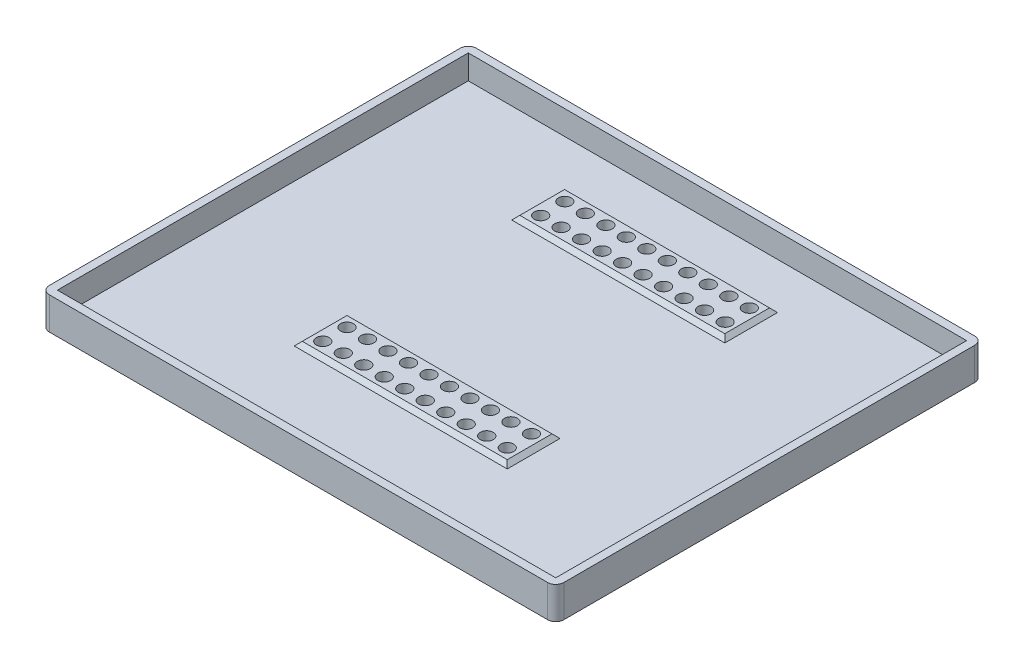
SolidWorks part; units mm, degrees
ref_plane "前视基准面" through (0, 0, 0) normal (0, 0, 1) x (1, 0, 0)
ref_plane "上视基准面" through (0, 0, 0) normal (0, 1, 0) x (1, 0, 0)
ref_plane "右视基准面" through (0, 0, 0) normal (1, 0, 0) x (0, 0, -1)
other "Configuration Table"
sketch "草图1" plane through (0, 0, 0) normal (0, 1, 0) x (1, 0, 0)
  line L1 (-39.7539, 20.0048) -> (24.0061, 20.0048)
  line L2 (-39.7539, 20.0048) -> (-39.7539, -32.9152)
  line L3 (-39.7539, -32.9152) -> (24.0061, -32.9152)
  line L4 (24.0061, 20.0048) -> (24.0061, -32.9152)
  dimension "D1" = 52.92
  dimension "D2" = 63.76
extrude "凸台-拉伸1" add sketch "草图1" along normal blind 1
fillet "圆角1" radius 1 4 edges at (24.0061, 0.5, 32.9152) (24.0061, 0.5, -20.0048) (-39.7539, 0.5, -20.0048) (-39.7539, 0.5, 32.9152)
sketch "草图2" plane through (0, 1, 0) normal (0, 1, 0) x (1, 0, 0)
  line L0 (23.0061, 20.0048) -> (-38.7539, 20.0048) construction
  line L1 (-20.6244, 12.8048) -> (4.7756, 12.8048)
  line L2 (-20.6244, 12.8048) -> (-20.6244, 7.2648)
  line L3 (-20.6244, 7.2648) -> (4.7756, 7.2648)
  line L4 (4.7756, 12.8048) -> (4.7756, 7.2648)
  line L5 (-20.5839, -14.1952) -> (4.8161, -14.1952)
  line L6 (-20.5839, -14.1952) -> (-20.5839, -19.7352)
  line L7 (-20.5839, -19.7352) -> (4.8161, -19.7352)
  line L8 (4.8161, -14.1952) -> (4.8161, -19.7352)
  line L9 (24.0061, -31.9152) -> (24.0061, 19.0048) construction
  line L10 (-38.7539, -32.9152) -> (23.0061, -32.9152) construction
  dimension "D1" = 25.4
  dimension "D2" = 5.54
  dimension "D3" = 7.2
  dimension "D4" = 19.2305
  dimension "D5" = 19.19
  dimension "D6" = 13.18
extrude "凸台-拉伸2" add sketch "草图2" along normal blind 0.5
chamfer "倒角1" distance 0.5 angle 45 8 edges at (4.8161, 1, 16.9652) (-7.8839, 1, 14.1952) (-7.8839, 1, 19.7352) (-20.5839, 1, 16.9652) (-20.6244, 1, -10.0348) (-7.9244, 1, -12.8048) (4.7756, 1, -10.0348) (-7.9244, 1, -7.2648)
sketch "草图3" plane through (0, 0, 0) normal (0, -1, 0) x (1, 0, 0)
  line L0 (-39.7539, -19.0048) -> (-39.7539, 31.9152) construction
  line L1 (-38.7539, 32.9152) -> (23.0061, 32.9152) construction
  line L2 (23.0061, -20.0048) -> (-38.7539, -20.0048) construction
  line L3 (-19.3139, -8.5348) -> (-16.7739, -8.5348) construction
  line L4 (-19.3139, -8.5348) -> (-19.3139, -11.5348) construction
  circle A0 centre (-19.3139, 18.4652) radius 0.8
  circle A1 centre (-16.7739, 18.4652) radius 0.8
  circle A2 centre (-14.2339, 18.4652) radius 0.8
  circle A3 centre (-11.6939, 18.4652) radius 0.8
  circle A4 centre (-9.1539, 18.4652) radius 0.8
  circle A5 centre (-6.6139, 18.4652) radius 0.8
  circle A6 centre (-4.0739, 18.4652) radius 0.8
  circle A7 centre (-1.5339, 18.4652) radius 0.8
  circle A8 centre (1.0061, 18.4652) radius 0.8
  circle A9 centre (3.5461, 18.4652) radius 0.8
  circle A10 centre (-16.7739, 15.4652) radius 0.8
  circle A11 centre (-14.2339, 15.4652) radius 0.8
  circle A12 centre (-11.6939, 15.4652) radius 0.8
  circle A13 centre (-9.1539, 15.4652) radius 0.8
  circle A14 centre (-6.6139, 15.4652) radius 0.8
  circle A15 centre (-4.0739, 15.4652) radius 0.8
  circle A16 centre (-1.5339, 15.4652) radius 0.8
  circle A17 centre (1.0061, 15.4652) radius 0.8
  circle A18 centre (3.5461, 15.4652) radius 0.8
  circle A19 centre (-19.3139, 15.4652) radius 0.8
  circle A20 centre (-19.3139, -8.5348) radius 0.8
  circle A21 centre (-16.7739, -8.5348) radius 0.8
  circle A22 centre (-14.2339, -8.5348) radius 0.8
  circle A23 centre (-11.6939, -8.5348) radius 0.8
  circle A24 centre (-9.1539, -8.5348) radius 0.8
  circle A25 centre (-6.6139, -8.5348) radius 0.8
  circle A26 centre (-4.0739, -8.5348) radius 0.8
  circle A27 centre (-1.5339, -8.5348) radius 0.8
  circle A28 centre (1.0061, -8.5348) radius 0.8
  circle A29 centre (3.5461, -8.5348) radius 0.8
  circle A30 centre (-16.7739, -11.5348) radius 0.8
  circle A31 centre (-14.2339, -11.5348) radius 0.8
  circle A32 centre (-11.6939, -11.5348) radius 0.8
  circle A33 centre (-9.1539, -11.5348) radius 0.8
  circle A34 centre (-6.6139, -11.5348) radius 0.8
  circle A35 centre (-4.0739, -11.5348) radius 0.8
  circle A36 centre (-1.5339, -11.5348) radius 0.8
  circle A37 centre (1.0061, -11.5348) radius 0.8
  circle A38 centre (3.5461, -11.5348) radius 0.8
  circle A39 centre (-19.3139, -11.5348) radius 0.8
  dimension "D1" = 1.6
  dimension "D6" = 11.47
  dimension "D2" = 20.44
  dimension "D3" = 14.45
  dimension "D4" = 10
  dimension "D5" = 2
  dimension "D9" = 2.54
  dimension "D10" = 3
  dimension "D7" = 10
  dimension "D8" = 2
extrude "切除-拉伸2" cut sketch "草图3" against normal through all
sketch "草图4" plane through (0, 1, 0) normal (0, 1, 0) x (1, 0, 0)
  line L0 (-38.7539, -31.9152) -> (23.0061, -31.9152)
  line L1 (23.0061, -31.9152) -> (23.0061, 19.0048)
  line L2 (23.0061, 19.0048) -> (-38.7539, 19.0048)
  line L3 (-38.7539, 19.0048) -> (-38.7539, -31.9152)
  line L4 (-38.7539, -32.9152) -> (23.0061, -32.9152)
  line L5 (24.0061, -31.9152) -> (24.0061, 19.0048)
  line L6 (23.0061, 20.0048) -> (-38.7539, 20.0048)
  line L7 (-39.7539, 19.0048) -> (-39.7539, -31.9152)
  line L8 (-38.7539, -32.9152) -> (23.0061, -32.9152)
  line L9 (24.0061, -31.9152) -> (24.0061, 19.0048)
  line L10 (23.0061, 20.0048) -> (-38.7539, 20.0048)
  line L11 (-39.7539, 19.0048) -> (-39.7539, -31.9152)
  arc A0 (23.0061, -31.9152) -> (23.0061, -31.9152) centre (23.0061, -31.9152) ccw
  arc A1 (23.0061, 19.0048) -> (23.0061, 19.0048) centre (23.0061, 19.0048) ccw
  arc A2 (-38.7539, 19.0048) -> (-38.7539, 19.0048) centre (-38.7539, 19.0048) ccw
  arc A3 (-38.7539, -31.9152) -> (-38.7539, -31.9152) centre (-38.7539, -31.9152) ccw
  arc A4 (23.0061, -32.9152) -> (24.0061, -31.9152) centre (23.0061, -31.9152) ccw
  arc A5 (24.0061, 19.0048) -> (23.0061, 20.0048) centre (23.0061, 19.0048) ccw
  arc A6 (-38.7539, 20.0048) -> (-39.7539, 19.0048) centre (-38.7539, 19.0048) ccw
  arc A7 (-39.7539, -31.9152) -> (-38.7539, -32.9152) centre (-38.7539, -31.9152) ccw
  arc A8 (23.0061, -32.9152) -> (24.0061, -31.9152) centre (23.0061, -31.9152) ccw
  arc A9 (24.0061, 19.0048) -> (23.0061, 20.0048) centre (23.0061, 19.0048) ccw
  arc A10 (-38.7539, 20.0048) -> (-39.7539, 19.0048) centre (-38.7539, 19.0048) ccw
  arc A11 (-39.7539, -31.9152) -> (-38.7539, -32.9152) centre (-38.7539, -31.9152) ccw
  dimension "D1" = 0
  dimension "D2" = 1
extrude "凸台-拉伸3" add sketch "草图4" along normal blind 3 contours L11 A11 L8 A8 L9 A9 L10 A10 | L3 A3 L0 A0 L1 A1 L2 A2
